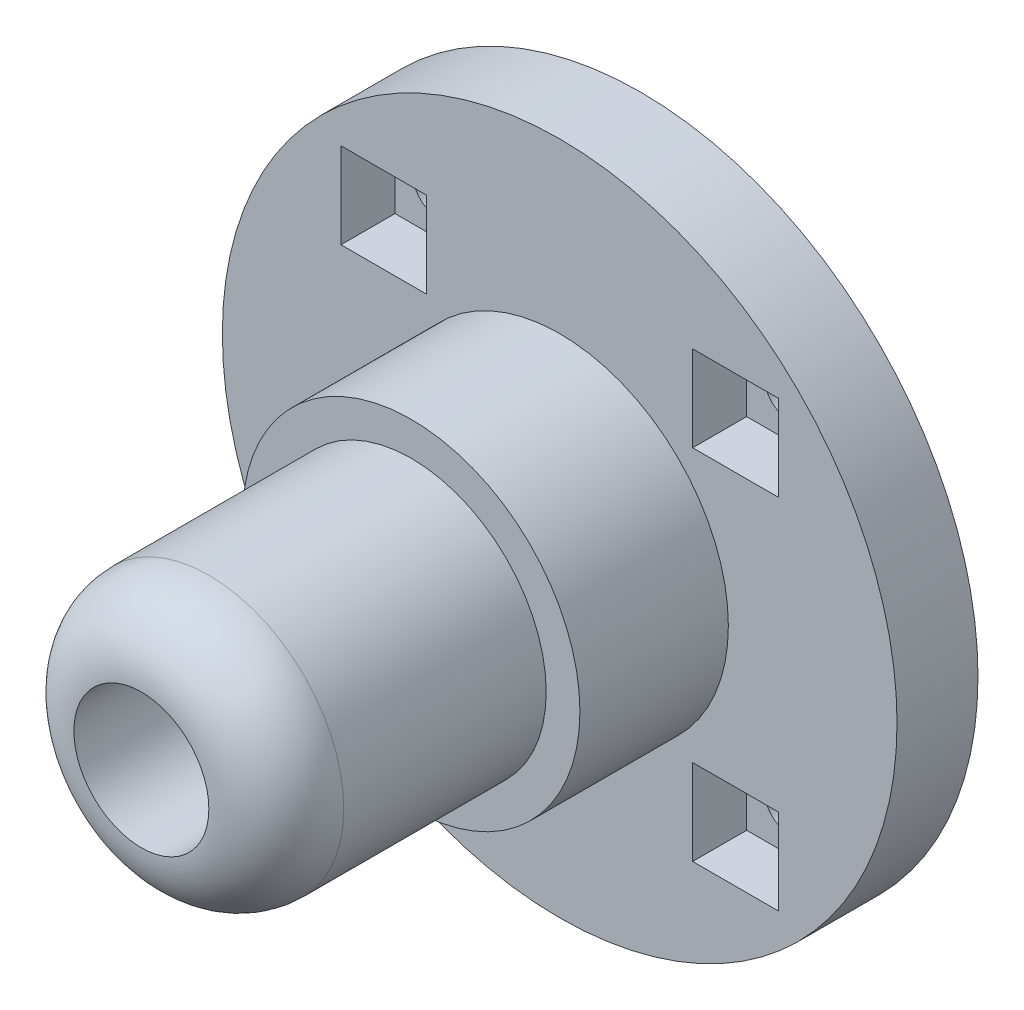
SolidWorks part; units mm, degrees
ref_plane "Front Plane" through (0, 0, 0) normal (0, 0, 1) x (1, 0, 0)
ref_plane "Top Plane" through (0, 0, 0) normal (0, 1, 0) x (1, 0, 0)
ref_plane "Right Plane" through (0, 0, 0) normal (1, 0, 0) x (0, 0, -1)
sketch "Sketch1" plane through (0, 0, 0) normal (0, 0, 1) x (1, 0, 0)
  circle A0 centre (0, 0) radius 25
  circle A1 centre (-13.0295, -13.2748) radius 1.85
  circle A2 centre (13.0295, -13.2748) radius 1.85
  circle A3 centre (13.0295, 13.2748) radius 1.85
  circle A4 centre (-13.0295, 13.2748) radius 1.85
  circle A5 centre (0, 0) radius 5
  arc A6 (4.0736, 24.6659) -> (4.0736, -24.6659) centre (0, 0) ccw construction
  circle A7 centre (-13.0295, -13.2748) radius 1.85 construction
  circle A8 centre (13.0295, -13.2748) radius 1.85 construction
  circle A9 centre (13.0295, 13.2748) radius 1.85 construction
  circle A10 centre (-13.0295, 13.2748) radius 1.85 construction
  circle A11 centre (0, 0) radius 5 construction
extrude "Boss-Extrude1" add sketch "Sketch1" along normal blind 6 contours A2 | A3 | A4 | A1 | A5 | A0 region at (-13.0295, -13.2748, 0) region at (13.0295, -13.2748, 0) region at (13.0295, 13.2748, 0) region at (-13.0295, 13.2748, 0) region at (0, 0, 0)
sketch "Sketch2" plane through (0, 0, 6) normal (0, 0, 1) x (1, 0, 0)
  circle A0 centre (0, 0) radius 12.5
  circle A1 centre (0, 0) radius 5
  circle A2 centre (0, 0) radius 5 construction
  dimension "D1" = 25
extrude "Boss-Extrude2" add sketch "Sketch2" along normal blind 11
sketch "Sketch3" plane through (0, 0, 17) normal (0, 0, 1) x (1, 0, 0)
  circle A0 centre (0, 0) radius 10
  circle A1 centre (0, 0) radius 5
  circle A2 centre (0, 0) radius 5 construction
  dimension "D1" = 20
extrude "Boss-Extrude3" add sketch "Sketch3" along normal blind 20
fillet "Fillet1" radius 5 1 edges at (10, 0, 37)
sketch "Sketch4" plane through (0, 0, 6) normal (0, 0, 1) x (1, 0, 0)
  line L0 (0, 0) -> (0, -50000) construction
  line L1 (16.2045, -10.0998) -> (9.8545, -10.0998)
  line L2 (16.2045, -10.0998) -> (16.2045, -16.4498)
  line L3 (16.2045, -16.4498) -> (9.8545, -16.4498)
  line L4 (9.8545, -10.0998) -> (9.8545, -16.4498)
  line L5 (16.2045, -10.0998) -> (9.8545, -16.4498) construction
  line L6 (16.2045, -16.4498) -> (9.8545, -10.0998) construction
  line L7 (0, 0) -> (-50000, 0) construction
  line L8 (16.2045, 16.4498) -> (9.8545, 10.0998) construction
  line L9 (16.2045, 10.0998) -> (9.8545, 16.4498) construction
  line L10 (9.8545, 10.0998) -> (9.8545, 16.4498)
  line L11 (16.2045, 16.4498) -> (9.8545, 16.4498)
  line L12 (16.2045, 10.0998) -> (16.2045, 16.4498)
  line L13 (16.2045, 10.0998) -> (9.8545, 10.0998)
  line L14 (-16.2045, 10.0998) -> (-9.8545, 16.4498) construction
  line L15 (-16.2045, 16.4498) -> (-9.8545, 10.0998) construction
  line L16 (-16.2045, -16.4498) -> (-9.8545, -10.0998) construction
  line L17 (-16.2045, -10.0998) -> (-9.8545, -16.4498) construction
  line L18 (-16.2045, 10.0998) -> (-9.8545, 10.0998)
  line L19 (-16.2045, 10.0998) -> (-16.2045, 16.4498)
  line L20 (-16.2045, 16.4498) -> (-9.8545, 16.4498)
  line L21 (-9.8545, 10.0998) -> (-9.8545, 16.4498)
  line L22 (-9.8545, -10.0998) -> (-9.8545, -16.4498)
  line L23 (-16.2045, -16.4498) -> (-9.8545, -16.4498)
  line L24 (-16.2045, -10.0998) -> (-16.2045, -16.4498)
  line L25 (-16.2045, -10.0998) -> (-9.8545, -10.0998)
  point P0 (13.0295, -13.2748)
  point P15 (13.0295, 13.2748)
  point P24 (-13.0295, 13.2748)
  point P25 (-13.0295, -13.2748)
  dimension "D1" = 6.35
extrude "Cut-Extrude1" cut sketch "Sketch4" against normal blind 4
